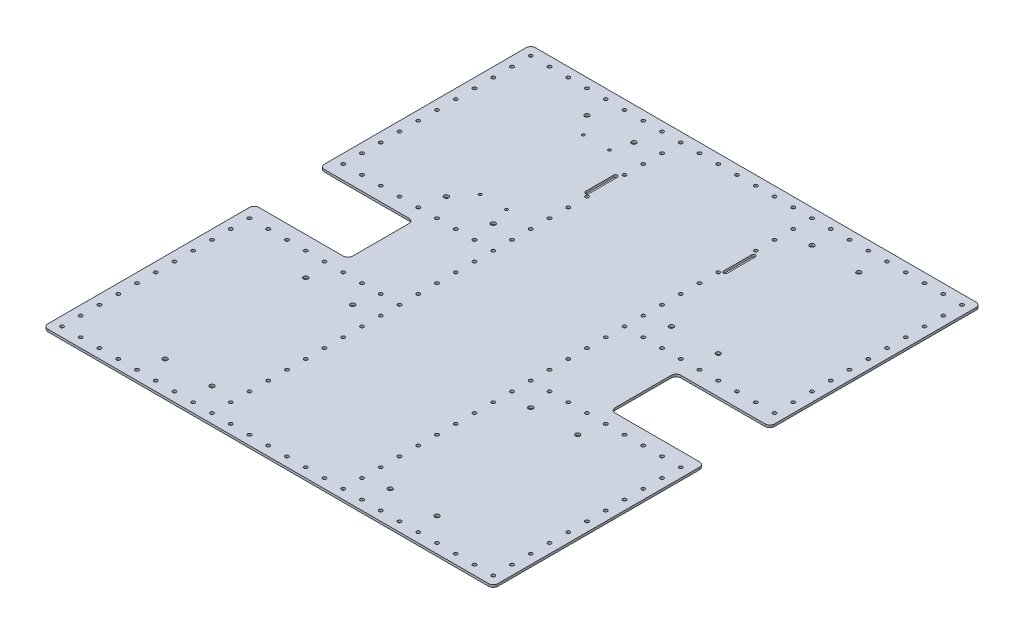
SolidWorks part; units mm, degrees
ref_plane "Front Plane" through (0, 0, 0) normal (0, 0, 1) x (1, 0, 0)
ref_plane "Top Plane" through (0, 0, 0) normal (0, 1, 0) x (1, 0, 0)
ref_plane "Right Plane" through (0, 0, 0) normal (1, 0, 0) x (0, 0, -1)
sketch "Sketch1" plane through (0, 0, 0) normal (0, 1, 0) x (1, 0, 0)
  line L1 (0, 0) -> (609.6, 0)
  line L2 (0, 0) -> (0, -660.4)
  line L3 (0, -660.4) -> (609.6, -660.4)
  line L4 (609.6, 0) -> (609.6, -660.4)
  line L5 (609.6, -285.75) -> (482.6, -285.75)
  line L6 (609.6, -285.75) -> (609.6, -374.65)
  line L7 (609.6, -374.65) -> (482.6, -374.65)
  line L8 (482.6, -285.75) -> (482.6, -374.65)
  line L9 (0, -285.75) -> (127, -285.75)
  line L10 (0, -285.75) -> (0, -374.65)
  line L11 (0, -374.65) -> (127, -374.65)
  line L12 (127, -285.75) -> (127, -374.65)
  dimension "D1" = 609.6
  dimension "D2" = 660.4
  dimension "D3" = 127
  dimension "D4" = 88.9
  dimension "D5" = 285.75
  dimension "D6" = 127
  dimension "D7" = 88.9
  dimension "D8" = 285.75
extrude "Boss-Extrude1" add sketch "Sketch1" along normal blind 3.175 contours L9 L12 L11 L2 L3 L4 L7 L8 L5 L1 region at (304.8, 0, 330.2)
sketch "Sketch2" plane through (0, 3.175, 0) normal (0, 1, 0) x (1, 0, 0)
  line L0 (0, 0) -> (0, -285.75) construction
  line L1 (0, -374.65) -> (0, -660.4) construction
  line L2 (0, -660.4) -> (609.6, -660.4) construction
  line L3 (0, 0) -> (609.6, 0) construction
  line L4 (0, -374.65) -> (0, -660.4) construction
  line L5 (0, -374.65) -> (127, -374.65) construction
  circle A452 centre (12.7, -647.7) radius 2.4
  circle A453 centre (38.1, -647.7) radius 2.4
  circle A454 centre (63.5, -647.7) radius 2.4
  circle A455 centre (88.9, -647.7) radius 2.4
  circle A456 centre (114.3, -647.7) radius 2.4
  circle A457 centre (139.7, -647.7) radius 2.4
  circle A458 centre (165.1, -647.7) radius 2.4
  circle A459 centre (190.5, -647.7) radius 2.4
  circle A460 centre (215.9, -647.7) radius 2.4
  circle A461 centre (241.3, -647.7) radius 2.4
  circle A462 centre (266.7, -647.7) radius 2.4
  circle A463 centre (292.1, -647.7) radius 2.4
  circle A464 centre (317.5, -647.7) radius 2.4
  circle A465 centre (342.9, -647.7) radius 2.4
  circle A466 centre (368.3, -647.7) radius 2.4
  circle A467 centre (393.7, -647.7) radius 2.4
  circle A468 centre (419.1, -647.7) radius 2.4
  circle A469 centre (444.5, -647.7) radius 2.4
  circle A470 centre (469.9, -647.7) radius 2.4
  circle A471 centre (495.3, -647.7) radius 2.4
  circle A472 centre (520.7, -647.7) radius 2.4
  circle A473 centre (546.1, -647.7) radius 2.4
  circle A474 centre (571.5, -647.7) radius 2.4
  circle A475 centre (596.9, -647.7) radius 2.4
  circle A476 centre (12.7, -622.3) radius 2.4
  circle A477 centre (12.7, -596.9) radius 2.4
  circle A478 centre (12.7, -571.5) radius 2.4
  circle A479 centre (12.7, -546.1) radius 2.4
  circle A480 centre (12.7, -520.7) radius 2.4
  circle A481 centre (12.7, -495.3) radius 2.4
  circle A482 centre (12.7, -469.9) radius 2.4
  circle A483 centre (12.7, -444.5) radius 2.4
  circle A484 centre (12.7, -419.1) radius 2.4
  circle A485 centre (12.7, -393.7) radius 2.4
  circle A486 centre (12.7, -622.3) radius 2.4
  circle A487 centre (596.9, -622.3) radius 2.4
  circle A488 centre (12.7, -596.9) radius 2.4
  circle A489 centre (596.9, -596.9) radius 2.4
  circle A490 centre (12.7, -571.5) radius 2.4
  circle A491 centre (596.9, -571.5) radius 2.4
  circle A492 centre (12.7, -546.1) radius 2.4
  circle A493 centre (596.9, -546.1) radius 2.4
  circle A494 centre (12.7, -520.7) radius 2.4
  circle A495 centre (596.9, -520.7) radius 2.4
  circle A496 centre (12.7, -495.3) radius 2.4
  circle A497 centre (596.9, -495.3) radius 2.4
  circle A498 centre (12.7, -469.9) radius 2.4
  circle A499 centre (596.9, -469.9) radius 2.4
  circle A500 centre (12.7, -444.5) radius 2.4
  circle A501 centre (596.9, -444.5) radius 2.4
  circle A502 centre (12.7, -419.1) radius 2.4
  circle A503 centre (596.9, -419.1) radius 2.4
  circle A504 centre (12.7, -393.7) radius 2.4
  circle A505 centre (596.9, -393.7) radius 2.4
  circle A506 centre (215.9, -622.3) radius 2.4
  circle A507 centre (393.7, -622.3) radius 2.4
  circle A508 centre (215.9, -596.9) radius 2.4
  circle A509 centre (393.7, -596.9) radius 2.4
  circle A510 centre (215.9, -571.5) radius 2.4
  circle A511 centre (393.7, -571.5) radius 2.4
  circle A512 centre (215.9, -546.1) radius 2.4
  circle A513 centre (393.7, -546.1) radius 2.4
  circle A514 centre (215.9, -520.7) radius 2.4
  circle A515 centre (393.7, -520.7) radius 2.4
  circle A516 centre (215.9, -495.3) radius 2.4
  circle A517 centre (393.7, -495.3) radius 2.4
  circle A518 centre (215.9, -469.9) radius 2.4
  circle A519 centre (393.7, -469.9) radius 2.4
  circle A520 centre (215.9, -444.5) radius 2.4
  circle A521 centre (393.7, -444.5) radius 2.4
  circle A522 centre (215.9, -419.1) radius 2.4
  circle A523 centre (393.7, -419.1) radius 2.4
  circle A524 centre (215.9, -393.7) radius 2.4
  circle A525 centre (393.7, -393.7) radius 2.4
  circle A526 centre (215.9, -368.3) radius 2.4
  circle A527 centre (393.7, -368.3) radius 2.4
  circle A528 centre (215.9, -342.9) radius 2.4
  circle A529 centre (393.7, -342.9) radius 2.4
  circle A530 centre (215.9, -317.5) radius 2.4
  circle A531 centre (393.7, -317.5) radius 2.4
  circle A532 centre (215.9, -292.1) radius 2.4
  circle A533 centre (393.7, -292.1) radius 2.4
  circle A534 centre (215.9, -266.7) radius 2.4
  circle A535 centre (393.7, -266.7) radius 2.4
  circle A536 centre (215.9, -241.3) radius 2.4
  circle A537 centre (393.7, -241.3) radius 2.4
  circle A538 centre (215.9, -215.9) radius 2.4
  circle A539 centre (393.7, -215.9) radius 2.4
  circle A540 centre (215.9, -190.5) radius 2.4
  circle A541 centre (393.7, -190.5) radius 2.4
  circle A542 centre (215.9, -165.1) radius 2.4
  circle A543 centre (393.7, -165.1) radius 2.4
  circle A544 centre (215.9, -139.7) radius 2.4
  circle A545 centre (393.7, -139.7) radius 2.4
  circle A546 centre (215.9, -114.3) radius 2.4
  circle A547 centre (393.7, -114.3) radius 2.4
  circle A548 centre (215.9, -88.9) radius 2.4
  circle A549 centre (393.7, -88.9) radius 2.4
  circle A550 centre (215.9, -63.5) radius 2.4
  circle A551 centre (393.7, -63.5) radius 2.4
  circle A552 centre (215.9, -38.1) radius 2.4
  circle A553 centre (393.7, -38.1) radius 2.4
  circle A554 centre (215.9, -12.7) radius 2.4
  circle A555 centre (393.7, -12.7) radius 2.4
  circle A556 centre (12.7, -12.7) radius 2.4
  circle A557 centre (38.1, -12.7) radius 2.4
  circle A558 centre (63.5, -12.7) radius 2.4
  circle A559 centre (88.9, -12.7) radius 2.4
  circle A560 centre (114.3, -12.7) radius 2.4
  circle A561 centre (139.7, -12.7) radius 2.4
  circle A562 centre (165.1, -12.7) radius 2.4
  circle A563 centre (190.5, -12.7) radius 2.4
  circle A564 centre (215.9, -12.7) radius 2.4
  circle A565 centre (241.3, -12.7) radius 2.4
  circle A566 centre (266.7, -12.7) radius 2.4
  circle A567 centre (292.1, -12.7) radius 2.4
  circle A568 centre (317.5, -12.7) radius 2.4
  circle A569 centre (342.9, -12.7) radius 2.4
  circle A570 centre (368.3, -12.7) radius 2.4
  circle A571 centre (393.7, -12.7) radius 2.4
  circle A572 centre (419.1, -12.7) radius 2.4
  circle A573 centre (444.5, -12.7) radius 2.4
  circle A574 centre (469.9, -12.7) radius 2.4
  circle A575 centre (495.3, -12.7) radius 2.4
  circle A576 centre (520.7, -12.7) radius 2.4
  circle A577 centre (546.1, -12.7) radius 2.4
  circle A578 centre (571.5, -12.7) radius 2.4
  circle A579 centre (596.9, -12.7) radius 2.4
  circle A580 centre (12.7, -38.1) radius 2.4
  circle A581 centre (12.7, -63.5) radius 2.4
  circle A582 centre (12.7, -88.9) radius 2.4
  circle A583 centre (12.7, -114.3) radius 2.4
  circle A584 centre (12.7, -139.7) radius 2.4
  circle A585 centre (12.7, -165.1) radius 2.4
  circle A586 centre (12.7, -190.5) radius 2.4
  circle A587 centre (12.7, -215.9) radius 2.4
  circle A588 centre (12.7, -241.3) radius 2.4
  circle A589 centre (12.7, -266.7) radius 2.4
  circle A590 centre (12.7, -38.1) radius 2.4
  circle A591 centre (596.9, -38.1) radius 2.4
  circle A592 centre (12.7, -63.5) radius 2.4
  circle A593 centre (596.9, -63.5) radius 2.4
  circle A594 centre (12.7, -88.9) radius 2.4
  circle A595 centre (596.9, -88.9) radius 2.4
  circle A596 centre (12.7, -114.3) radius 2.4
  circle A597 centre (596.9, -114.3) radius 2.4
  circle A598 centre (12.7, -139.7) radius 2.4
  circle A599 centre (596.9, -139.7) radius 2.4
  circle A600 centre (12.7, -165.1) radius 2.4
  circle A601 centre (596.9, -165.1) radius 2.4
  circle A602 centre (12.7, -190.5) radius 2.4
  circle A603 centre (596.9, -190.5) radius 2.4
  circle A604 centre (12.7, -215.9) radius 2.4
  circle A605 centre (596.9, -215.9) radius 2.4
  circle A606 centre (12.7, -241.3) radius 2.4
  circle A607 centre (596.9, -241.3) radius 2.4
  circle A608 centre (12.7, -266.7) radius 2.4
  circle A609 centre (596.9, -266.7) radius 2.4
  dimension "D3" = 12.7
  dimension "D4" = 24
  dimension "D5" = 11
  dimension "D6" = 11
  dimension "D7" = 26
  dimension "D8" = 4.8
  dimension "D1" = 4.8
  dimension "D9" = 12.7
  dimension "D11" = 24
  dimension "D2" = 12.7
  dimension "D10" = 12.7
  dimension "D12" = 11
  dimension "D13" = 11
extrude "Cut-Extrude1" cut sketch "Sketch2" against normal blind 119.634
sketch "Sketch3" plane through (0, 3.175, 0) normal (0, 1, 0) x (1, 0, 0)
  line L0 (609.6, -393.7) -> (0, -393.7)
  line L1 (304.8, -660.4) -> (304.8, 0)
  line L2 (609.6, -374.65) -> (609.6, -660.4) construction
  line L3 (0, -374.65) -> (0, -660.4) construction
  line L4 (609.6, -374.65) -> (482.6, -374.65) construction
  line L5 (0, -660.4) -> (609.6, -660.4) construction
  line L6 (0, 0) -> (609.6, 0) construction
  line L7 (127, -330.2) -> (482.6, -330.2)
  line L8 (127, -285.75) -> (127, -374.65) construction
  line L9 (482.6, -285.75) -> (482.6, -374.65) construction
  circle A0 centre (546.1, -393.7) radius 2.425
  circle A1 centre (571.5, -393.7) radius 2.425
  circle A2 centre (520.7, -393.7) radius 2.425
  circle A3 centre (495.3, -393.7) radius 2.425
  circle A4 centre (469.9, -393.7) radius 2.425
  circle A5 centre (444.5, -393.7) radius 2.425
  circle A6 centre (419.1, -393.7) radius 2.425
  circle A7 centre (190.5, -393.7) radius 2.425
  circle A8 centre (165.1, -393.7) radius 2.425
  circle A9 centre (139.7, -393.7) radius 2.425
  circle A10 centre (114.3, -393.7) radius 2.425
  circle A11 centre (88.9, -393.7) radius 2.425
  circle A12 centre (38.1, -393.7) radius 2.425
  circle A13 centre (63.5, -393.7) radius 2.425
  circle A14 centre (63.5, -266.7) radius 2.425
  circle A15 centre (38.1, -266.7) radius 2.425
  circle A16 centre (88.9, -266.7) radius 2.425
  circle A17 centre (114.3, -266.7) radius 2.425
  circle A18 centre (139.7, -266.7) radius 2.425
  circle A19 centre (165.1, -266.7) radius 2.425
  circle A20 centre (190.5, -266.7) radius 2.425
  circle A21 centre (419.1, -266.7) radius 2.425
  circle A22 centre (444.5, -266.7) radius 2.425
  circle A23 centre (469.9, -266.7) radius 2.425
  circle A24 centre (495.3, -266.7) radius 2.425
  circle A25 centre (520.7, -266.7) radius 2.425
  circle A26 centre (571.5, -266.7) radius 2.425
  circle A27 centre (546.1, -266.7) radius 2.425
  dimension "D2" = 4.85
  dimension "D3" = 38.1
  dimension "D4" = 7
  dimension "D1" = 19.05
extrude "Cut-Extrude2" cut sketch "Sketch3" against normal through all contours A7 L0 | A7 L0 | A8 L0 | A8 L0 | A9 L0 | A9 L0 | A10 L0 | A10 L0 | A11 L0 | A11 L0 | A12 L0 | A12 L0 | L0 A6 | L0 A6 | L0 A5 | L0 A5 | L0 A4 | L0 A4 | L0 A3 | L0 A3 | L0 A2 | L0 A2 | L0 A0 | L0 A0 | L0 A1 | L0 A1 | A13 L0 | A13 L0 region at (571.5, 3.175, 394.7292) region at (571.5, 3.175, 392.6708) region at (38.1, 3.175, 394.7292) region at (38.1, 3.175, 392.6708) region at (63.5, 3.175, 394.7292) region at (63.5, 3.175, 392.6708) region at (88.9, 3.175, 394.7292) region at (88.9, 3.175, 392.6708) region at (114.3, 3.175, 394.7292) region at (114.3, 3.175, 392.6708) region at (139.7, 3.175, 394.7292) region at (139.7, 3.175, 392.6708) region at (165.1, 3.175, 394.7292) region at (165.1, 3.175, 392.6708) region at (190.5, 3.175, 394.7292) region at (190.5, 3.175, 392.6708) region at (419.1, 3.175, 394.7292) region at (419.1, 3.175, 392.6708) region at (444.5, 3.175, 394.7292) region at (444.5, 3.175, 392.6708) region at (469.9, 3.175, 394.7292) region at (469.9, 3.175, 392.6708) region at (495.3, 3.175, 394.7292) region at (495.3, 3.175, 392.6708) region at (520.7, 3.175, 394.7292) region at (520.7, 3.175, 392.6708) region at (546.1, 3.175, 394.7292) region at (546.1, 3.175, 392.6708)
extrude "Cut-Extrude3" cut sketch "Sketch3<3>" against normal through all contours A15 | A14 | A16 | A17 | A18 | A19 | A20 | A21 | A22 | A24 | A23 | A25 | A27 | A26 | A21 | A22 region at (63.5, 3.175, 266.7) region at (38.1, 3.175, 266.7) region at (88.9, 3.175, 266.7) region at (114.3, 3.175, 266.7) region at (139.7, 3.175, 266.7) region at (165.1, 3.175, 266.7) region at (190.5, 3.175, 266.7) region at (419.1, 3.175, 266.7) region at (444.5, 3.175, 266.7) region at (469.9, 3.175, 266.7) region at (495.3, 3.175, 266.7) region at (520.7, 3.175, 266.7) region at (571.5, 3.175, 266.7) region at (546.1, 3.175, 266.7)
sketch "Sketch3<3>" plane through (0, 3.175, 0) normal (0, 1, 0) x (1, 0, 0) same geometry as "Sketch3"
sketch "Sketch4" plane through (0, 3.175, 0) normal (0, 1, 0) x (1, 0, 0)
  line L0 (0, 0) -> (609.6, 0) construction
  line L5 (425.45, -44.45) -> (488.95, -44.45)
  line L6 (425.45, -44.45) -> (425.45, -234.95)
  line L7 (425.45, -234.95) -> (488.95, -234.95)
  line L8 (488.95, -44.45) -> (488.95, -234.95)
  line L9 (609.6, 0) -> (609.6, -285.75) construction
  line L10 (609.6, -285.75) -> (482.6, -285.75) construction
  line L11 (304.8, 0) -> (304.8, -660.4)
  line L12 (0, -660.4) -> (609.6, -660.4) construction
  line L13 (127, -330.2) -> (482.6, -330.2)
  line L14 (127, -285.75) -> (127, -374.65) construction
  line L15 (482.6, -285.75) -> (482.6, -374.65) construction
  line L16 (120.65, -44.45) -> (120.65, -234.95)
  line L17 (184.15, -234.95) -> (120.65, -234.95)
  line L18 (184.15, -44.45) -> (184.15, -234.95)
  line L19 (184.15, -44.45) -> (120.65, -44.45)
  line L20 (184.15, -615.95) -> (120.65, -615.95)
  line L21 (184.15, -615.95) -> (184.15, -425.45)
  line L22 (184.15, -425.45) -> (120.65, -425.45)
  line L23 (120.65, -615.95) -> (120.65, -425.45)
  line L24 (488.95, -615.95) -> (488.95, -425.45)
  line L25 (425.45, -425.45) -> (488.95, -425.45)
  line L26 (425.45, -615.95) -> (425.45, -425.45)
  line L27 (425.45, -615.95) -> (488.95, -615.95)
  circle A18 centre (425.45, -44.45) radius 3.1
  circle A19 centre (488.95, -44.45) radius 3.1
  circle A20 centre (488.95, -234.95) radius 3.0934
  circle A21 centre (425.45, -234.95) radius 3.1
  circle A22 centre (184.15, -234.95) radius 3.1
  circle A23 centre (120.65, -234.95) radius 3.0934
  circle A24 centre (120.65, -44.45) radius 3.1
  circle A25 centre (184.15, -44.45) radius 3.1
  circle A26 centre (184.15, -615.95) radius 3.1
  circle A27 centre (120.65, -615.95) radius 3.1
  circle A28 centre (120.65, -425.45) radius 3.0934
  circle A29 centre (184.15, -425.45) radius 3.1
  circle A30 centre (425.45, -425.45) radius 3.1
  circle A31 centre (488.95, -425.45) radius 3.0934
  circle A32 centre (488.95, -615.95) radius 3.1
  circle A33 centre (425.45, -615.95) radius 3.1
  circle A34 centre (147.8513, -125.3052) radius 21.4946
  dimension "D1" = 63.5
  dimension "D2" = 190.5
  dimension "D6" = 6.2
  dimension "D7" = 6.2
  dimension "D8" = 6.1867
  dimension "D9" = 6.2
  dimension "D3" = 44.45
  dimension "D4" = 120.65
  dimension "D5" = 50.8
extrude "Cut-Extrude4" cut sketch "Sketch4" against normal through all contours A24 L16 L19 | A24 L19 L16 | A25 L19 L18 | A25 L18 L19 | A22 L18 L17 | A22 L17 L18 | A23 L16 L17 | A23 L17 L16 | L7 A20 L8 | L8 A20 L7 | L7 A21 L6 | L6 A21 L7 | L8 A19 L5 | L5 A19 L8 | L5 A18 L6 | L6 A18 L5 | A31 L24 L25 | A31 L25 L24 | A30 L25 L26 | A30 L26 L25 | A32 L24 L27 | A32 L27 L24 | A33 L26 L27 | A33 L27 L26 | L20 A26 L21 | L21 A26 L20 | L20 A27 L23 | L23 A27 L20 | L22 A29 L21 | L21 A29 L22 | L23 A28 L22 | L22 A28 L23 | A31 region at (425.0114, 3.175, 44.0114) region at (426.7657, 3.175, 45.7657) region at (489.3886, 3.175, 44.0114) region at (487.6343, 3.175, 45.7657) region at (426.7657, 3.175, 233.6343) region at (425.0114, 3.175, 235.3886) region at (489.3876, 3.175, 235.3876) region at (487.6371, 3.175, 233.6371) region at (121.9657, 3.175, 45.7657) region at (120.2114, 3.175, 44.0114) region at (121.9629, 3.175, 233.6371) region at (120.2124, 3.175, 235.3876) region at (184.5886, 3.175, 44.0114) region at (182.8343, 3.175, 45.7657) region at (182.8343, 3.175, 233.6343) region at (184.5886, 3.175, 235.3886) region at (120.2114, 3.175, 616.3886) region at (121.9657, 3.175, 614.6343) region at (182.8343, 3.175, 614.6343) region at (184.5886, 3.175, 616.3886) region at (120.2124, 3.175, 425.0124) region at (121.9629, 3.175, 426.7629) region at (182.8343, 3.175, 426.7657) region at (184.5886, 3.175, 425.0114) region at (487.6343, 3.175, 614.6343) region at (489.3886, 3.175, 616.3886) region at (487.6371, 3.175, 426.7629) region at (489.3876, 3.175, 425.0124) region at (425.0114, 3.175, 616.3886) region at (426.7657, 3.175, 614.6343) region at (426.7657, 3.175, 426.7657) region at (425.0114, 3.175, 425.0114)
fillet "Fillet1" radius 6.35 12 edges at (0, 1.5875, 285.75) (609.6, 1.5875, 0) (609.6, 1.5875, 285.75) (482.6, 1.5875, 285.75) (482.6, 1.5875, 374.65) (609.6, 1.5875, 374.65) (609.6, 1.5875, 660.4) (0, 1.5875, 660.4) (0, 1.5875, 374.65) (127, 1.5875, 374.65) (127, 1.5875, 285.75) (0, 1.5875, 0)
sketch "Sketch5" plane through (0, 3.175, 0) normal (0, 1, 0) x (1, 0, 0)
  line L1 (140.97, -69.85) -> (176.53, -69.85)
  line L2 (140.97, -69.85) -> (140.97, -209.55)
  line L3 (140.97, -209.55) -> (176.53, -209.55)
  line L4 (176.53, -69.85) -> (176.53, -209.55)
  circle A0 centre (120.65, -44.45) radius 3.1 construction
  circle A1 centre (140.97, -69.85) radius 1.905
  circle A2 centre (176.53, -69.85) radius 1.905
  circle A3 centre (176.53, -209.55) radius 1.905
  circle A4 centre (140.97, -209.55) radius 1.905
  dimension "D4" = 20.32
  dimension "D5" = 3.81
  dimension "D6" = 3.81
  dimension "D7" = 3.81
  dimension "D8" = 3.81
  dimension "D1" = 35.56
  dimension "D2" = 139.7
  dimension "D3" = 25.4
extrude "Cut-Extrude5" cut sketch "Sketch5" against normal through all contours L1 A1 L2 | L2 A1 L1 | L4 A2 L1 | L1 A2 L4 | L3 A3 L4 | L4 A3 L3 | L3 A4 L2 | L2 A4 L3 region at (140.7005, 3.175, 69.5805) region at (141.7785, 3.175, 70.6585) region at (176.7995, 3.175, 69.5805) region at (175.7215, 3.175, 70.6585) region at (141.7785, 3.175, 208.7415) region at (140.7005, 3.175, 209.8195) region at (176.7995, 3.175, 209.8195) region at (175.7215, 3.175, 208.7415)
sketch "Sketch6" plane through (0, 3.175, 0) normal (0, 1, 0) x (1, 0, 0)
  line L0 (213.5, -88.9) -> (218.3, -88.9)
  line L1 (215.9, -86.5) -> (215.9, -91.3)
  line L2 (211.328, -96.52) -> (211.328, -134.62) construction
  line L3 (215.9, -88.9) -> (211.328, -88.9)
  line L4 (215.9, -88.9) -> (215.9, -96.52)
  line L5 (215.9, -96.52) -> (211.328, -96.52)
  line L6 (211.328, -88.9) -> (211.328, -96.52)
  line L7 (213.868, -96.52) -> (213.868, -134.62)
  line L8 (208.788, -96.52) -> (208.788, -134.62)
  line L9 (304.8, 0) -> (304.8, -129.3666)
  line L10 (6.35, 0) -> (603.25, 0) construction
  line L11 (398.272, -96.52) -> (398.272, -134.62) construction
  line L12 (395.732, -96.52) -> (395.732, -134.62)
  line L13 (400.812, -96.52) -> (400.812, -134.62)
  line L14 (398.272, -88.9) -> (398.272, -96.52)
  line L15 (393.7, -96.52) -> (398.272, -96.52)
  line L16 (393.7, -88.9) -> (393.7, -96.52)
  line L17 (393.7, -88.9) -> (398.272, -88.9)
  line L18 (393.7, -86.5) -> (393.7, -91.3)
  line L19 (396.1, -88.9) -> (391.3, -88.9)
  circle A0 centre (215.9, -88.9) radius 2.4 construction
  arc A1 (213.868, -96.52) -> (208.788, -96.52) centre (211.328, -96.52) ccw
  arc A2 (208.788, -134.62) -> (213.868, -134.62) centre (211.328, -134.62) ccw
  circle A3 centre (215.9, -114.3) radius 2.4
  arc A4 (395.732, -96.52) -> (400.812, -96.52) centre (398.272, -96.52) cw
  arc A5 (400.812, -134.62) -> (395.732, -134.62) centre (398.272, -134.62) cw
  circle A6 centre (393.7, -114.3) radius 2.4
  point P11 (211.328, -115.57)
  point P26 (398.272, -115.57)
  dimension "D1" = 4.572
  dimension "D2" = 7.62
  dimension "D3" = 38.1
  dimension "D4" = 5.08
extrude "Cut-Extrude6" cut sketch "Sketch6" against normal through all contours L5 A1 L6 | A3 L7 L5 L6 A1 L8 A2 | A4 L15 L14 | L12 A6 A5 L13 A4 L14 L15 region at (212.406, 3.175, 95.442) region at (211.2944, 3.175, 116.064) region at (398.3056, 3.175, 116.064) region at (397.194, 3.175, 95.442)
extrude "Boss-Extrude2" add sketch "Sketch6<3>" against normal blind 3.175 contours L7 A3 | A6 L12 region at (215.9795, 3.175, 114.3) region at (393.6205, 3.175, 114.3)
sketch "Sketch6<3>" plane through (0, 3.175, 0) normal (0, 1, 0) x (1, 0, 0) same geometry as "Sketch6"
